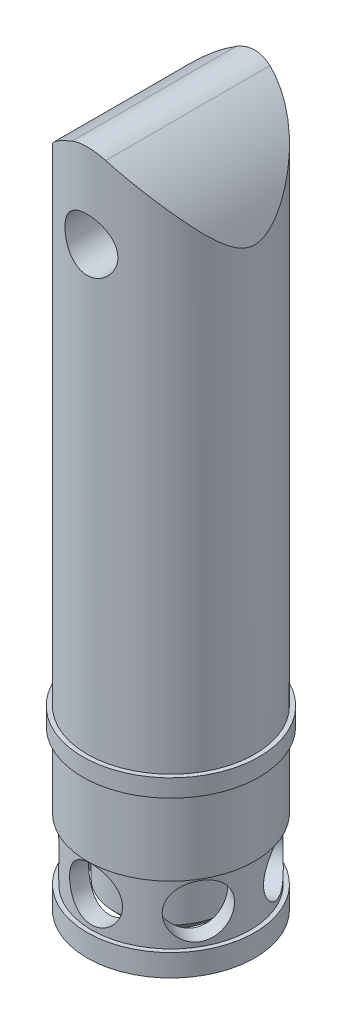
SolidWorks part; units mm, degrees
ref_plane "Front Plane" through (0, 0, 0) normal (0, 0, 1) x (1, 0, 0)
ref_plane "Top Plane" through (0, 0, 0) normal (0, 1, 0) x (1, 0, 0)
ref_plane "Right Plane" through (0, 0, 0) normal (1, 0, 0) x (0, 0, -1)
sketch "Sketch1" plane through (0, 0, 0) normal (0, 1, 0) x (1, 0, 0)
  circle A0 centre (0, 0) radius 4.75
  dimension "D1" = 9.5
extrude "Boss-Extrude1" add sketch "Sketch1" against normal blind 40
sketch "Sketch2" plane through (0, 0, 0) normal (0, 0, 1) x (1, 0, 0)
  line L0 (-4.75, -5) -> (-4.75, 0)
  line L1 (-4.75, 0) -> (-4.75, -40) construction
  line L3 (4.75, 0) -> (4.75, -5)
  line L4 (4.75, -40) -> (4.75, 0) construction
  line L5 (4.75, -5) -> (-4.75, -5) construction
  line L6 (0, 0) -> (0, -5) construction
  line L7 (-4.75, 0) -> (0, 2)
  line L8 (0, 2) -> (4.75, 0)
  arc A0 (-4.75, -5) -> (0, 0) centre (2.8585, -7.4719) cw
  arc A1 (4.75, -5) -> (0, 0) centre (-2.8585, -7.4719) ccw
  point P16 (0, -0.7714)
  point P17 (0, 0)
  point P19 (-0.4157, 1.9876)
  point P20 (0, 0)
  point P21 (0, 0)
  point P22 (0, 0)
  dimension "D2" = 8
  dimension "D1" = 5
  dimension "D3" = 7
extrude "Cut-Extrude1" cut sketch "Sketch2" against normal through all both and the other way through all
fillet "Fillet1" radius 2 1 edges at (0, 0, 0)
sketch "Sketch3" plane through (0, 0, 0) normal (0, 0, 1) x (1, 0, 0)
  line L0 (4.75, -40) -> (4.75, -4.9999) construction
  line L1 (4.75, -31) -> (5, -31)
  line L2 (4.75, -31) -> (4.75, -30)
  line L3 (4.75, -30) -> (5, -30)
  line L4 (5, -31) -> (5, -30)
  line L5 (-4.75, -40) -> (4.75, -40) construction
  dimension "D1" = 0.25
  dimension "D2" = 1
  dimension "D3" = 9
revolve "Revolve1" add sketch "Sketch3" angle 360 about axis through (0, -40, 0) along (0, 1, 0)
sketch "Sketch4" plane through (0, 0, 0) normal (0, 0, 1) x (1, 0, 0)
  line L0 (-4.75, -40) -> (4.75, -40) construction
  circle A0 centre (0, -37) radius 1.5
  point P2 (0, 0)
  dimension "D1" = 3
  dimension "D2" = 3
extrude "Cut-Extrude2" cut sketch "Sketch4" against normal through all both and the other way through all
pattern_circular "CirPattern1" count 3 over 360 about axis through (0, -40, 0) along (0, 1, 0) of "Cut-Extrude2" reverse direction yes
sketch "Sketch5" plane through (0, 0, 0) normal (0, 0, 1) x (1, 0, 0)
  line L0 (-4.25, -40) -> (-3.5, -38.5)
  line L1 (-4.75, -40) -> (4.75, -40) construction
  line L2 (-3.5, -38.5) -> (-3.5, -33)
  line L3 (-3.5, -33) -> (0, -33)
  line L4 (0, -33) -> (0, -40)
  line L5 (-4.25, -40) -> (0, -40)
  line L6 (-4.75, -31) -> (-4.75, -40) construction
  dimension "D1" = 7
  dimension "D2" = 3.5
  dimension "D3" = 0.5
  dimension "D4" = 1.5
revolve "Cut-Revolve1" cut sketch "Sketch5" angle 360 about L4
sketch "Sketch6" plane through (0, 0, 0) normal (0, 0, 1) x (1, 0, 0)
  line L0 (4.75, -40) -> (4.75, -31) construction
  line L1 (4.75, -38.75) -> (4.5, -38.75)
  line L2 (4.75, -38.75) -> (4.75, -35.25)
  line L3 (4.75, -35.25) -> (4.5, -35.25)
  line L4 (4.5, -38.75) -> (4.5, -35.25)
  line L5 (-4.75, -40) -> (4.75, -40) construction
  point P6 (4.75, -37)
  dimension "D1" = 3
  dimension "D2" = 3.5
  dimension "D3" = 0.25
revolve "Cut-Revolve2" cut sketch "Sketch6" angle 360 about axis through (0, -40, 0) along (0, 1, 0)
sketch "Sketch7" plane through (0, 0, 0) normal (0, 0, 1) x (1, 0, 0)
  line L0 (-3.2, -38.5) -> (-3.2, -33)
  line L1 (-3.2, -33) -> (0, -33)
  line L2 (0, -33) -> (0, -40)
  line L3 (-4.25, -40) -> (4.25, -40) construction
  line L4 (-3.5, -33) -> (3.5, -33) construction
  line L9 (-3.5, -38.5) -> (-3.0311, -38.5) construction
  arc A0 (-3.2, -38.5) -> (0, -40) centre (0, -35.8367) ccw
  dimension "D1" = 3.2
revolve "Revolve2" add sketch "Sketch7" angle 360 about L2
sketch "Sketch8" plane through (0, 0, 0) normal (0, 0, 1) x (1, 0, 0)
  circle A0 centre (0, -5) radius 1.5
  point P2 (0, 0)
  dimension "D2" = 3
  dimension "D1" = 5
extrude "Cut-Extrude3" cut sketch "Sketch8" against normal through all both and the other way through all
